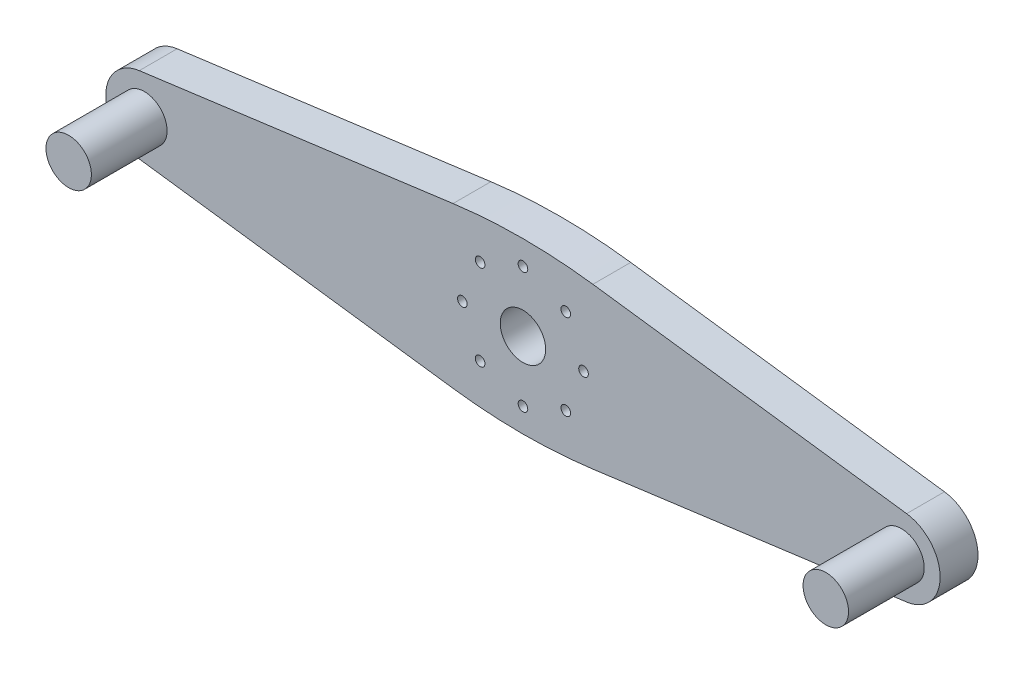
SolidWorks part; units mm, degrees
material "ABS"
ref_plane "Płaszczyzna przednia" through (0, 0, 0) normal (0, 0, 1) x (1, 0, 0)
ref_plane "Płaszczyzna górna" through (0, 0, 0) normal (0, 1, 0) x (1, 0, 0)
ref_plane "Płaszczyzna prawa" through (0, 0, 0) normal (1, 0, 0) x (0, 0, -1)
sketch "Szkic1" plane through (0, 0, 0) normal (0, 0, 1) x (1, 0, 0)
  line L0 (-44.521, 0) -> (57.4684, 0) construction
  line L1 (0, 0) -> (0, 26.3225) construction
  line L2 (-50.6729, 5.0557) -> (-9.2351, 10.5708)
  line L3 (-50.6729, -5.0557) -> (-9.2351, -10.5708)
  line L4 (50.6729, -5.0557) -> (9.2351, -10.5708)
  line L5 (50.6729, 5.0557) -> (9.2351, 10.5708)
  circle A0 centre (0, 0) radius 3
  circle A1 centre (-5.6569, 5.6569) radius 0.635
  circle A2 centre (-8, 0) radius 0.635
  circle A3 centre (0, 8) radius 0.635
  circle A4 centre (5.6569, 5.6569) radius 0.635
  circle A5 centre (-50, 0) radius 3
  circle A6 centre (50, 0) radius 3
  arc A7 (-50.6729, 5.0557) -> (-50.6729, -5.0557) centre (-50, 0) ccw
  arc A8 (50.6729, 5.0557) -> (50.6729, -5.0557) centre (50, 0) cw
  arc A9 (-9.2351, 10.5708) -> (9.2351, 10.5708) centre (0, -58.8174) cw
  arc A10 (-9.2351, -10.5708) -> (9.2351, -10.5708) centre (0, 58.8174) ccw
  circle A11 centre (8, 0) radius 0.635
  circle A12 centre (5.6569, -5.6569) radius 0.635
  circle A13 centre (0, -8) radius 0.635
  circle A14 centre (-5.6569, -5.6569) radius 0.635
  point P16 (0, 0)
  point P28 (0, 11.7999)
  point P31 (0, -11.7999)
  point P41 (0, 0)
  dimension "D1" = 8
  dimension "D2" = 50
  dimension "D3" = 6
  dimension "D4" = 6
  dimension "D5" = 1.27
  dimension "D7" = 70
  dimension "D8" = 21.1415
extrude "Dodanie-wyciągnięcie1" add sketch "Szkic1" along normal blind 5
extrude "Dodanie-wyciągnięcie2" add sketch "Szkic1<2>" along normal blind 15 contours A5 | A6 region at (-50, 0, 0) region at (50, 0, 0)
sketch "Szkic1<2>" plane through (0, 0, 0) normal (0, 0, 1) x (1, 0, 0) same geometry as "Szkic1"
